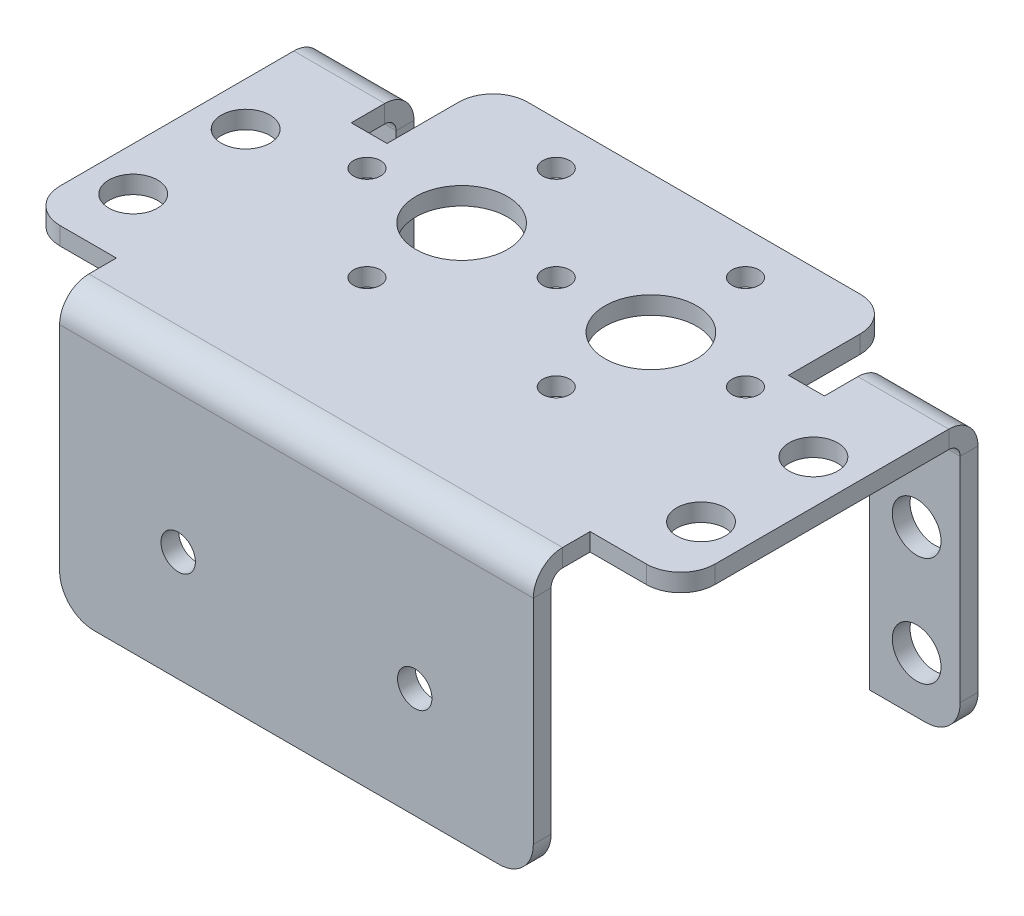
SolidWorks part; units mm, degrees
note: The reader was unsure of these and kept them because the rebuilt part matched: flange length of "Edge-Flange1", "Edge-Flange2".
ref_plane "Front Plane" through (0, 0, 0) normal (0, 0, 1) x (1, 0, 0)
ref_plane "Top Plane" through (0, 0, 0) normal (0, 1, 0) x (1, 0, 0)
ref_plane "Right Plane" through (0, 0, 0) normal (1, 0, 0) x (0, 0, -1)
sketch "Sketch1" plane through (0, 0, 0) normal (0, 1, 0) x (1, 0, 0)
  line L0 (25.55, -13.15) -> (20.65, -13.15)
  line L1 (-28.55, -16.55) -> (28.55, -16.55)
  line L2 (-28.55, -16.55) -> (-28.55, 16.55)
  line L3 (-28.55, 16.55) -> (28.55, 16.55)
  line L4 (28.55, -16.55) -> (28.55, 16.55)
  line L5 (-28.55, -16.55) -> (28.55, 16.55) construction
  line L6 (-28.55, 16.55) -> (28.55, -16.55) construction
  line L7 (20.65, -13.15) -> (20.65, -16.55)
  line L8 (28.55, 10.22) -> (20.625, 10.22)
  line L9 (20.625, 10.22) -> (20.625, 7.3)
  line L10 (20.625, 7.3) -> (17.5, 7.3)
  line L11 (17.5, 7.3) -> (17.5, 13.55)
  line L12 (0, -55) -> (0, 55) construction
  line L13 (-25.55, -13.15) -> (-20.65, -13.15)
  line L14 (-20.65, -13.15) -> (-20.65, -16.55)
  line L15 (-28.55, 10.22) -> (-20.625, 10.22)
  line L16 (-20.625, 10.22) -> (-20.625, 7.3)
  line L17 (-20.625, 7.3) -> (-17.5, 7.3)
  line L18 (-17.5, 7.3) -> (-17.5, 13.55)
  arc A0 (25.55, -13.15) -> (28.55, -10.15) centre (25.55, -10.15) ccw
  arc A1 (17.5, 13.55) -> (14.5, 16.55) centre (14.5, 13.55) ccw
  arc A2 (-25.55, -13.15) -> (-28.55, -10.15) centre (-25.55, -10.15) cw
  arc A3 (-17.5, 13.55) -> (-14.5, 16.55) centre (-14.5, 13.55) cw
  circle A4 centre (24.75, -7.58) radius 2.125
  circle A5 centre (24.75, 2.22) radius 2.125
  circle A6 centre (8.25, 4.55) radius 4
  circle A7 centre (8.25, -3.7) radius 1.175
  circle A8 centre (0, 4.55) radius 1.175
  circle A9 centre (8.25, 12.8) radius 1.175
  circle A10 centre (16.5, 4.55) radius 1.175
  circle A11 centre (-24.75, 2.22) radius 2.125
  circle A12 centre (-24.75, -7.58) radius 2.125
  circle A13 centre (-8.25, -3.7) radius 1.175
  circle A14 centre (-16.5, 4.55) radius 1.175
  circle A15 centre (-8.25, 4.55) radius 4
  circle A16 centre (-8.25, 12.8) radius 1.175
  point P0 (0, 0)
  point P20 (20.625, 8.76)
  point P30 (-20.625, 8.76)
  point P52 (8.25, 4.55)
  dimension "D5" = 6
  dimension "D10" = 4.25
  dimension "D15" = 8
  dimension "D16" = 2.35
  dimension "D1" = 33.1
  dimension "D2" = 57.1
  dimension "D3" = 3.4
  dimension "D4" = 20.65
  dimension "D6" = 20.625
  dimension "D7" = 17.5
  dimension "D8" = 26.77
  dimension "D9" = 9.25
  dimension "D11" = 9.8
  dimension "D12" = 8
  dimension "D13" = 24.75
  dimension "D17" = 8.25
  dimension "D18" = 12
  dimension "D14" = 4
sketch "Sketch2" plane through (0, 0, 0) normal (0, 1, 0) x (1, 0, 0)
  line L0 (28.55, 10.22) -> (20.625, 10.22) construction
  line L1 (20.625, 10.22) -> (20.625, 7.3) construction
  line L2 (20.625, 7.3) -> (17.5, 7.3) construction
  line L3 (17.5, 7.3) -> (17.5, 13.55) construction
  line L4 (-28.55, -16.55) -> (28.55, -16.55)
  line L5 (28.55, -16.55) -> (28.55, 16.55)
  line L6 (28.55, 16.55) -> (-28.55, 16.55)
  line L7 (-28.55, 16.55) -> (-28.55, -16.55)
  line L8 (-20.65, -16.55) -> (20.65, -16.55)
  line L9 (28.55, -10.15) -> (28.55, 10.22)
  line L10 (14.5, 16.55) -> (-14.5, 16.55)
  line L11 (-28.55, 10.22) -> (-28.55, -10.15)
  line L12 (20.65, -13.15) -> (20.65, -16.55) construction
  line L13 (25.55, -13.15) -> (20.65, -13.15) construction
  line L14 (-20.65, -13.15) -> (-20.65, -16.55) construction
  line L15 (-25.55, -13.15) -> (-20.65, -13.15) construction
  line L16 (-28.55, 10.22) -> (-20.625, 10.22) construction
  line L17 (-20.625, 10.22) -> (-20.625, 7.3) construction
  line L18 (-20.625, 7.3) -> (-17.5, 7.3) construction
  line L19 (-17.5, 7.3) -> (-17.5, 13.55) construction
  line L20 (28.55, 10.22) -> (20.625, 10.22)
  line L21 (20.625, 10.22) -> (20.625, 7.3)
  line L22 (20.625, 7.3) -> (17.5, 7.3)
  line L23 (17.5, 7.3) -> (17.5, 13.55)
  line L24 (20.65, -13.15) -> (20.65, -16.55)
  line L25 (25.55, -13.15) -> (20.65, -13.15)
  line L26 (-20.65, -13.15) -> (-20.65, -16.55)
  line L27 (-25.55, -13.15) -> (-20.65, -13.15)
  line L28 (-28.55, 10.22) -> (-20.625, 10.22)
  line L29 (-20.625, 10.22) -> (-20.625, 7.3)
  line L30 (-20.625, 7.3) -> (-17.5, 7.3)
  line L31 (-17.5, 7.3) -> (-17.5, 13.55)
  arc A0 (17.5, 13.55) -> (14.5, 16.55) centre (14.5, 13.55) ccw construction
  circle A1 centre (0, 4.55) radius 1.175
  circle A2 centre (0, 4.55) radius 1.175
  circle A3 centre (8.25, -3.7) radius 1.175
  circle A4 centre (8.25, -3.7) radius 1.175
  circle A5 centre (8.25, 4.55) radius 4
  circle A6 centre (8.25, 4.55) radius 4
  circle A7 centre (24.75, 2.22) radius 2.125
  circle A8 centre (24.75, 2.22) radius 2.125
  circle A9 centre (24.75, -7.58) radius 2.125
  circle A10 centre (24.75, -7.58) radius 2.125
  circle A11 centre (-16.5, 4.55) radius 1.175
  circle A12 centre (-16.5, 4.55) radius 1.175
  circle A13 centre (-8.25, -3.7) radius 1.175
  circle A14 centre (-8.25, -3.7) radius 1.175
  circle A15 centre (-24.75, -7.58) radius 2.125
  circle A16 centre (-24.75, -7.58) radius 2.125
  circle A17 centre (-24.75, 2.22) radius 2.125
  circle A18 centre (-24.75, 2.22) radius 2.125
  circle A19 centre (16.5, 4.55) radius 1.175
  circle A20 centre (16.5, 4.55) radius 1.175
  circle A21 centre (8.25, 12.8) radius 1.175
  circle A22 centre (8.25, 12.8) radius 1.175
  circle A23 centre (-8.25, 12.8) radius 1.175
  circle A24 centre (-8.25, 12.8) radius 1.175
  circle A25 centre (-8.25, 4.55) radius 4
  circle A26 centre (-8.25, 4.55) radius 4
  arc A27 (25.55, -13.15) -> (28.55, -10.15) centre (25.55, -10.15) ccw construction
  arc A28 (-28.55, -10.15) -> (-25.55, -13.15) centre (-25.55, -10.15) ccw construction
  arc A29 (-14.5, 16.55) -> (-17.5, 13.55) centre (-14.5, 13.55) ccw construction
  arc A30 (17.5, 13.55) -> (14.5, 16.55) centre (14.5, 13.55) ccw
  arc A31 (25.55, -13.15) -> (28.55, -10.15) centre (25.55, -10.15) ccw
  arc A32 (-28.55, -10.15) -> (-25.55, -13.15) centre (-25.55, -10.15) ccw
  arc A33 (-14.5, 16.55) -> (-17.5, 13.55) centre (-14.5, 13.55) ccw
  dimension "D1" = 0
  dimension "D2" = 0
  dimension "D3" = 0
  dimension "D4" = 0
  dimension "D5" = 0
  dimension "D6" = 0
  dimension "D7" = 0
  dimension "D8" = 0
  dimension "D9" = 0
  dimension "D10" = 0
  dimension "D11" = 0
  dimension "D12" = 0
  dimension "D13" = 0
  dimension "D14" = 0
base flange "Base-Flange1" sketch "Sketch2" thickness 1.55 reverse thickness direction no parameters "D1"=10
edge flange "Edge-Flange1" sketch "Sketch11" flange profiles "Sketch11", "Sketch12" flange angle 90 flange length 24.15 flange position bend outside bend radius 1 thickness 1.55 relief rectangular parameters "D6"=10, "D8"=1
sketch "Sketch11" plane through (0, -1.55, -10.22) normal (0, 0, -1) x (1, 0, 0)
  line L2 (-28.55, 0) -> (-28.55, 22.6)
  line L3 (-28.55, 22.6) -> (-20.625, 22.6)
  line L4 (-20.625, 22.6) -> (-20.625, 0)
  line L7 (-20.625, 0) -> (-28.55, 0) construction
  line L8 (-20.625, 0) -> (-28.55, 0)
sketch "Sketch12" plane through (0, -1.55, -10.22) normal (0, 0, -1) x (1, 0, 0)
  line L2 (20.625, 0) -> (20.625, 22.6)
  line L3 (20.625, 22.6) -> (28.55, 22.6)
  line L4 (28.55, 22.6) -> (28.55, 0)
  line L7 (28.55, 0) -> (20.625, 0) construction
  line L8 (28.55, 0) -> (20.625, 0)
bend "EdgeBend1" bend radius 1 bend angle 90 parameters "D5"=1
bend "EdgeBend2" bend radius 1 bend angle 90 parameters "D5"=2
edge flange "Edge-Flange2" sketch "Sketch15" flange angle 90 flange length 24.15 flange position material outside bend radius 1 thickness 1.55 relief rectangular parameters "D6"=10
sketch "Sketch15" plane through (0, -1.55, 16.55) normal (0, 0, 1) x (-1, 0, 0)
  line L2 (-20.65, 0) -> (-20.65, 22.6)
  line L3 (-20.65, 22.6) -> (20.65, 22.6)
  line L4 (20.65, 22.6) -> (20.65, 0)
  line L7 (20.65, 0) -> (-20.65, 0) construction
  line L8 (20.65, 0) -> (-20.65, 0)
bend "EdgeBend3" bend radius 1 bend angle 90 parameters "D5"=3
fillet "Fillet1" radius 3 4 edges at (28.55, -24.15, -11.995) (20.65, -24.15, 17.325) (-20.65, -24.15, 17.325) (-28.55, -24.15, -11.995)
sketch "Sketch16" plane through (0, 0, -12.77) normal (0, 0, -1) x (-1, 0, 0)
  line L0 (20.625, -24.15) -> (25.55, -24.15) construction
  line L1 (26.875, -9.8) -> (22.625, -9.8) construction
  line L2 (22.625, -1.55) -> (26.875, -1.55) construction
  line L5 (0, 13.2825) -> (0, -13.2825) construction
  circle A0 centre (24.75, -19.3) radius 2.125
  circle A1 centre (24.75, -9.8) radius 2.125
  circle A2 centre (10.3124, -14.55) radius 1.5
  circle A3 centre (-24.75, -9.8) radius 2.125
  circle A4 centre (-24.75, -19.3) radius 2.125
  circle A5 centre (-10.3124, -14.55) radius 1.5
  circle A6 centre (10.3124, -14.55) radius 1.55 construction
  point P8 (24.75, -9.8)
  point P11 (24.75, -1.55)
  dimension "D5" = 3
  dimension "D1" = 9.5
  dimension "D2" = 4.85
extrude "Cut-Extrude1" cut sketch "Sketch16" against normal through all normal cut yes
sketch "Sketch17" plane through (0, 0, -12.77) normal (0, 0, -1) x (-1, 0, 0)
  line L0 (-24.75, -19.3) -> (-24.75, -9.8) construction
  point P0 (-24.75, -19.3)
  point P1 (-24.75, -9.8)
  point P6 (-24.75, -14.55)
ref_plane "Plane1" through (0, -14.55, 0) normal (0, -1, 0) x (-1, 0, 0)
sketch "Bend-Lines1" [suppressed] plane through (0, 0, 0) normal (0, 1, 0) x (1, 0, 0)
sketch "Bounding-Box1" [suppressed] plane through (0, 0, 0) normal (0, 1, 0) x (1, 0, 0)
sheet metal parameters "Sheet-Metal1" thickness 1.55 parameters "D1"=10
flat pattern "Flat-Pattern1" [suppressed]
sketch "Bend-Lines2" plane through (0, 0, 0) normal (0, 1, 0) x (1, 0, 0)
sketch3d "Bounding-Box2" [suppressed]
  line L0 (43.05, -31.7, 0) -> (-14.05, -31.7, 0) construction
  line L1 (43.05, 3, 0) -> (-14.05, 3, 0) construction
  line L2 (43.05, -31.7, 0) -> (43.05, 3, 0) construction
  line L3 (-14.05, -31.7, 0) -> (-14.05, 3, 0) construction
sheet metal parameters "Sheet-Metal2" thickness 1.55 parameters "D1"=10
flat pattern "Flat-Pattern1"
sketch "Bend-Lines2" plane through (0, 0, 0) normal (0, 1, 0) x (1, 0, 0)
  line L0 (28.55, 14.8141) -> (20.625, 14.8141) construction
  line L1 (-20.625, 14.8141) -> (-28.55, 14.8141) construction
  line L2 (28.55, 14.8141) -> (20.625, 14.8141) construction
  line L3 (-20.625, 14.8141) -> (-28.55, 14.8141) construction
sketch3d "Bounding-Box2" [suppressed]
  line L0 (-43.05, -31.7, 0) -> (14.05, -31.7, 0) construction
  line L1 (-43.05, 23.4582, 0) -> (14.05, 23.4582, 0) construction
  line L2 (-43.05, -31.7, 0) -> (-43.05, 23.4582, 0) construction
  line L3 (14.05, -31.7, 0) -> (14.05, 23.4582, 0) construction
bend of the flat pattern "Flatten-<EdgeBend1>1"
bend of the flat pattern "Flatten-<EdgeBend2>1"
sheet metal parameters "Sheet-Metal3" thickness 1.55 parameters "D1"=10
flat pattern "Flat-Pattern1"
sketch "Bend-Lines2" plane through (0, 0, 0) normal (0, 1, 0) x (1, 0, 0)
  line L0 (28.55, 15.6141) -> (20.625, 15.6141) construction
  line L1 (-20.625, 15.6141) -> (-28.55, 15.6141) construction
  line L2 (28.55, 15.6141) -> (20.625, 15.6141) construction
  line L3 (-20.625, 15.6141) -> (-28.55, 15.6141) construction
  line L4 (-20.65, -16.9441) -> (20.65, -16.9441) construction
  line L5 (-20.65, -16.9441) -> (20.65, -16.9441) construction
sketch3d "Bounding-Box2" [suppressed]
  line L0 (14.05, 25.0582, 0) -> (14.05, -53.4882, 0) construction
  line L1 (-43.05, 25.0582, 0) -> (-43.05, -53.4882, 0) construction
  line L2 (14.05, 25.0582, 0) -> (-43.05, 25.0582, 0) construction
  line L3 (14.05, -53.4882, 0) -> (-43.05, -53.4882, 0) construction
bend of the flat pattern "Flatten-<EdgeBend1>1"
bend of the flat pattern "Flatten-<EdgeBend2>1"
bend of the flat pattern "Flatten-<EdgeBend3>1"
sheet metal parameters "Sheet-Metal4" thickness 1.55 parameters "D1"=10
flat pattern "Flat-Pattern1" [suppressed]
sketch "Bend-Lines2" plane through (0, 0, 0) normal (0, 1, 0) x (1, 0, 0)
  line L0 (28.55, 11.6141) -> (20.625, 11.6141) construction
  line L1 (-20.625, 11.6141) -> (-28.55, 11.6141) construction
  line L2 (28.55, 11.6141) -> (20.625, 11.6141) construction
  line L3 (-20.625, 11.6141) -> (-28.55, 11.6141) construction
  line L4 (-20.65, -16.9441) -> (20.65, -16.9441) construction
  line L5 (-20.65, -16.9441) -> (20.65, -16.9441) construction
sketch3d "Bounding-Box2" [suppressed]
  line L0 (14.05, 21.0582, 0) -> (14.05, -53.4882, 0) construction
  line L1 (-43.05, 21.0582, 0) -> (-43.05, -53.4882, 0) construction
  line L2 (14.05, 21.0582, 0) -> (-43.05, 21.0582, 0) construction
  line L3 (14.05, -53.4882, 0) -> (-43.05, -53.4882, 0) construction
bend of the flat pattern "Flatten-<EdgeBend1>1"
bend of the flat pattern "Flatten-<EdgeBend2>1"
bend of the flat pattern "Flatten-<EdgeBend3>1"
sketch "Sketch17-1" plane through (0, 0, -10.4582) normal (0, 1, 0) x (-1, 0, 0)
  line L0 (-24.75, -19.3) -> (-24.75, -9.8) construction
  point P0 (-24.75, -19.3)
  point P1 (-24.75, -9.8)
  point P6 (-24.75, -14.55)
